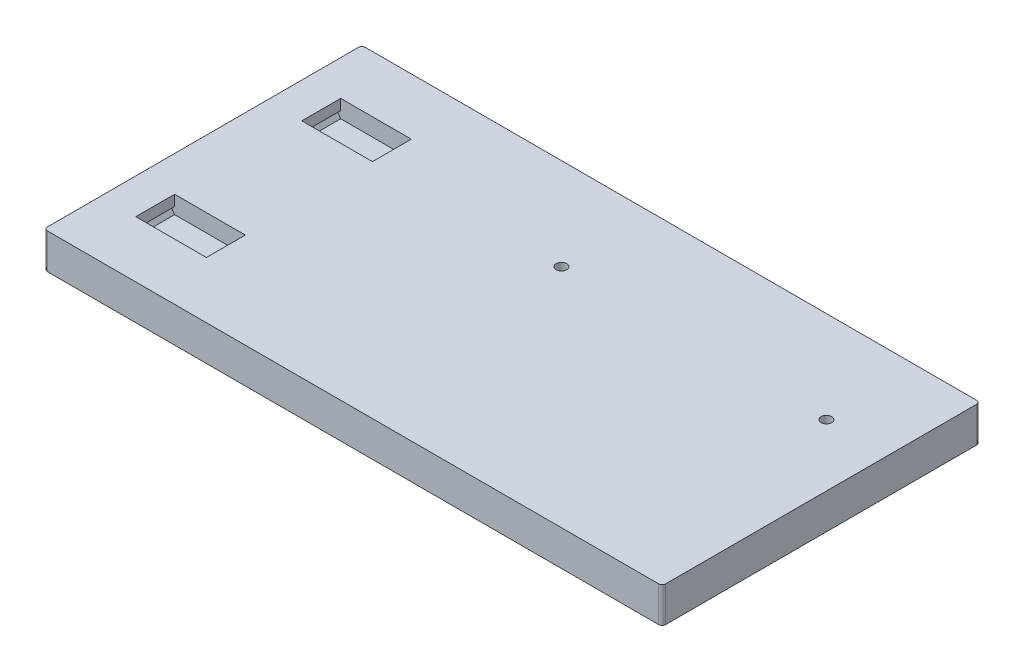
SolidWorks part; units mm, degrees
ref_plane "Front Plane" through (0, 0, 0) normal (0, 0, 1) x (1, 0, 0)
ref_plane "Top Plane" through (0, 0, 0) normal (0, 1, 0) x (1, 0, 0)
ref_plane "Right Plane" through (0, 0, 0) normal (1, 0, 0) x (0, 0, -1)
sketch "Sketch1" plane through (0, 0, 0) normal (0, 1, 0) x (1, 0, 0)
  line L1 (87.5, -45) -> (-87.5, -45)
  line L2 (87.5, -45) -> (87.5, 45)
  line L3 (87.5, 45) -> (-87.5, 45)
  line L4 (-87.5, -45) -> (-87.5, 45)
  line L5 (87.5, -45) -> (-87.5, 45) construction
  line L6 (87.5, 45) -> (-87.5, -45) construction
  point P0 (0, 0)
  dimension "D1" = 175
  dimension "D2" = 90
extrude "Boss-Extrude1" add sketch "Sketch1" along normal blind 10
sketch "Sketch2" plane through (0, 10, 0) normal (0, 1, 0) x (1, 0, 0)
  line L0 (-87.5, 45) -> (-87.5, -45) construction
  line L5 (-67.5, -23.5) -> (-67.5, 0) construction
  line L6 (-77.5, -29) -> (-57.5, -29)
  line L7 (0, 0) -> (-87.5, 0) construction
  line L8 (-77.5, -29) -> (-77.5, -18)
  line L9 (-77.5, -18) -> (-57.5, -18)
  line L10 (-57.5, -29) -> (-57.5, -18)
  line L11 (-77.5, -29) -> (-57.5, -18) construction
  line L12 (-77.5, -18) -> (-57.5, -29) construction
  circle A0 centre (-5, 19) radius 1.5
  circle A1 centre (70, 19) radius 1.5
  point P0 (-67.5, -23.5)
  point P13 (0, 0)
  point P14 (0, 0)
  point P17 (0, 0)
  dimension "D6" = 19
  dimension "D8" = 3
  dimension "D1" = 20
  dimension "D2" = 11
  dimension "D3" = 23.5
  dimension "D4" = 20
  dimension "D5" = 62.5
  dimension "D7" = 75
extrude "Cut-Extrude1" cut sketch "Sketch2" against normal blind 5 contours L6 L10 L9 L8 region at (-67.5, 10, 23.5)
ref_plane "Plane1" through (0, 0, 18) normal (0, 0, 1) x (1, 0, 0)
sketch "Sketch7" plane through (0, 0, 18) normal (0, 0, 1) x (1, 0, 0)
  line L0 (-77.5, 5) -> (-77.5, 10) construction
  line L2 (-77.5, 5) -> (-78.9004, 7)
  line L3 (-78.9004, 7) -> (-77.8004, 7)
  line L9 (-77.5, 5) -> (-76.8456, 5) construction
  line L10 (-77.5, 5) -> (-77.5, 7)
  line L11 (-77.5, 7) -> (-77.8004, 7)
  line L12 (-77.5, 5) -> (-57.5, 5) construction
  line L13 (-77.5, 5) -> (-77.5, 10) construction
  line L14 (-67.5, 10) -> (-67.5, 5) construction
  line L15 (-77.5, 10) -> (-57.5, 10) construction
  line L16 (-57.5, 5) -> (-57.5, 10) construction
  line L21 (-57.5, 5) -> (-57.5, 7)
  line L22 (-57.5, 5) -> (-56.0996, 7)
  line L23 (-57.5, 7) -> (-57.1996, 7)
  line L24 (-56.0996, 7) -> (-57.1996, 7)
  point P1 (0, 0)
  dimension "D1" = 1.1
  dimension "D2" = 125
  dimension "D3" = 2
extrude "Cut-Extrude2" cut sketch "Sketch7" along normal up to surface (11 mm away) up to face at (-67.5, 7.5, 29)
mirror "Mirror1" about plane through (0, 0, 0) normal (0, 0, 1) of "Cut-Extrude2", "Cut-Extrude1"
fillet "Fillet1" radius 1 4 edges at (-87.5, 5, -45) (87.5, 5, -45) (87.5, 5, 45) (-87.5, 5, 45)
extrude "Cut-Extrude3" cut sketch "Sketch2<8>" against normal through all contours A0 | A1
sketch "Sketch2<8>" plane through (0, 10, 0) normal (0, 1, 0) x (1, 0, 0) same geometry as "Sketch2"
